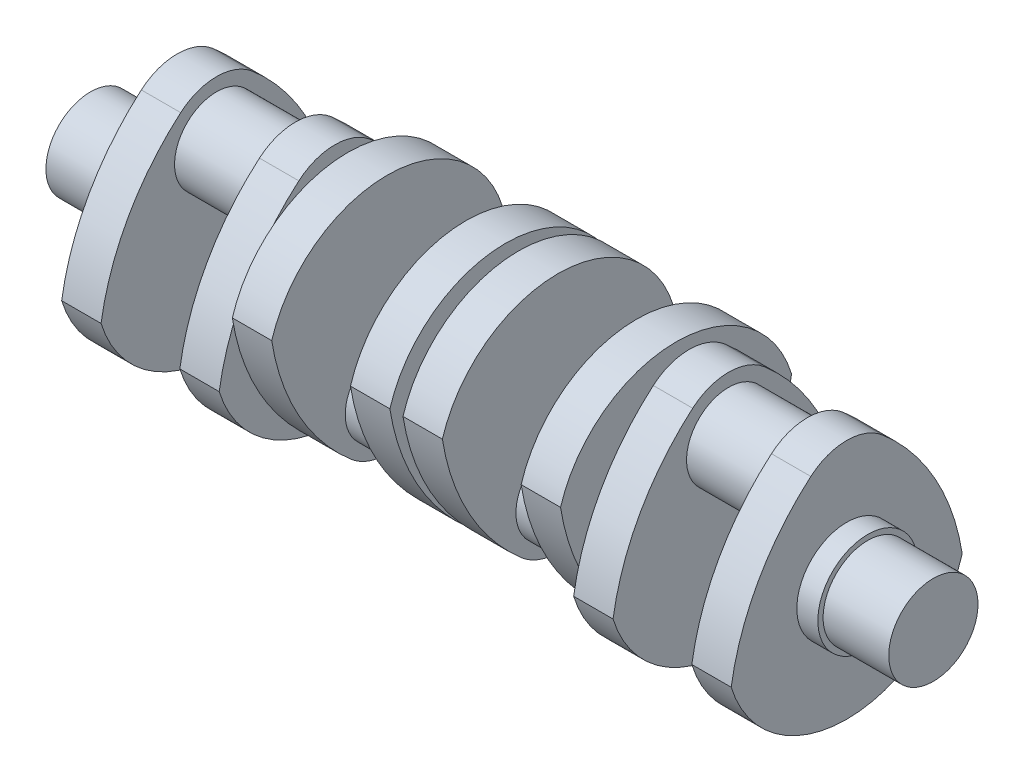
SolidWorks part; units mm, degrees
ref_plane "Front Plane" through (0, 0, 0) normal (0, 0, 1) x (1, 0, 0)
ref_plane "Top Plane" through (0, 0, 0) normal (0, 1, 0) x (1, 0, 0)
ref_plane "Right Plane" through (0, 0, 0) normal (1, 0, 0) x (0, 0, -1)
sketch "Sketch1" plane through (0, 0, 0) normal (1, 0, 0) x (0, 0, -1)
  circle A0 centre (0, 0) radius 17
  circle A1 centre (0, 0) radius 19
  dimension "D1" = 38
  dimension "D2" = 34
extrude "Boss-Extrude1" add sketch "Sketch1" against normal blind 25 contours A0
extrude "Boss-Extrude2" add sketch "Sketch1<3>" along normal blind 8 contours A1
sketch "Sketch1<3>" plane through (0, 0, 0) normal (1, 0, 0) x (0, 0, -1) same geometry as "Sketch1"
sketch "Sketch2" plane through (8, 0, 0) normal (1, 0, 0) x (0, 0, -1)
  arc A0 (-13.6681, 40.9431) -> (13.6681, 40.9431) centre (0, 25) cw
  arc A1 (-44, -13.4164) -> (44, -13.4164) centre (0, 0) ccw
  arc A2 (-13.6681, 40.9431) -> (-44, -13.4164) centre (44.9095, -27.3845) ccw
  arc A3 (13.6681, 40.9431) -> (44, -13.4164) centre (-44.9095, -27.3845) cw
  dimension "D3" = 46
  dimension "D4" = 21
  dimension "D5" = 90
  dimension "D6" = 90
  dimension "D1" = 25
  dimension "D2" = 88
extrude "Boss-Extrude3" add sketch "Sketch2" along normal blind 15
sketch "Sketch3" plane through (23, 0, 0) normal (1, 0, 0) x (0, 0, -1)
  circle A0 centre (0, 25) radius 16
  dimension "D1" = 32
extrude "Boss-Extrude4" add sketch "Sketch3" along normal blind 15
mirror "Mirror1" about plane through (38, 25, 0) normal (1, 0, 0) of "Boss-Extrude4", "Boss-Extrude3"
sketch "Sketch4" plane through (68, 0, 0) normal (1, 0, 0) x (0, 0, -1)
  circle A0 centre (0, 0) radius 17
  dimension "D1" = 34
extrude "Boss-Extrude5" add sketch "Sketch4" along normal blind 5
sketch "Sketch5" plane through (73, 0, 0) normal (1, 0, 0) x (0, 0, -1)
  arc A8 (-13.6681, -40.9431) -> (13.6681, -40.9431) centre (0, -25) ccw
  arc A9 (-44, 13.4164) -> (-13.6681, -40.9431) centre (44.9095, 27.3845) ccw
  arc A10 (44, 13.4164) -> (-44, 13.4164) centre (0, 0) ccw
  arc A11 (13.6681, -40.9431) -> (44, 13.4164) centre (-44.9095, 27.3845) ccw
extrude "Boss-Extrude6" add sketch "Sketch5" along normal blind 15
sketch "Sketch6" plane through (88, 0, 0) normal (1, 0, 0) x (0, 0, -1)
  circle A0 centre (0, -25) radius 16
  dimension "D1" = 32
  dimension "D2" = 25
extrude "Boss-Extrude7" add sketch "Sketch6" along normal blind 30
sketch "Sketch7" plane through (118, 0, 0) normal (1, 0, 0) x (0, 0, -1)
  arc A4 (-13.6681, -40.9431) -> (13.6681, -40.9431) centre (0, -25) ccw
  arc A5 (13.6681, -40.9431) -> (44, 13.4164) centre (-44.9095, 27.3845) ccw
  arc A6 (44, 13.4164) -> (-44, 13.4164) centre (0, 0) ccw
  arc A7 (-44, 13.4164) -> (-13.6681, -40.9431) centre (44.9095, 27.3845) ccw
  arc A8 (-13.6681, -40.9431) -> (13.6681, -40.9431) centre (0, -25) ccw
  arc A9 (13.6681, -40.9431) -> (44, 13.4164) centre (-44.9095, 27.3845) ccw
  arc A10 (44, 13.4164) -> (-44, 13.4164) centre (0, 0) ccw
  arc A11 (-44, 13.4164) -> (-13.6681, -40.9431) centre (44.9095, 27.3845) ccw
  dimension "D1" = 0
extrude "Boss-Extrude8" add sketch "Sketch7" along normal blind 15
sketch "Sketch8" plane through (133, 0, 0) normal (1, 0, 0) x (0, 0, -1)
  circle A0 centre (0, 0) radius 17
  dimension "D1" = 34
extrude "Boss-Extrude9" add sketch "Sketch8" along normal blind 2.5
mirror "Mirror2" about plane through (135.5, 0, 0) normal (1, 0, 0) of bodies 110
